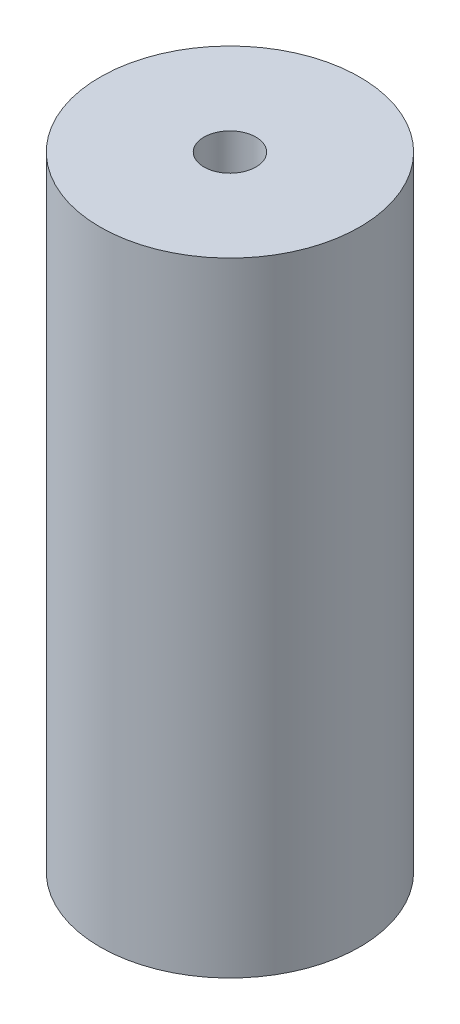
SolidWorks part; units mm, degrees
ref_plane "Plan de face" through (0, 0, 0) normal (0, 0, 1) x (1, 0, 0)
ref_plane "Plan de dessus" through (0, 0, 0) normal (0, 1, 0) x (1, 0, 0)
ref_plane "Plan de droite" through (0, 0, 0) normal (1, 0, 0) x (0, 0, -1)
sketch "Esquisse1" plane through (0, 0, 0) normal (0, 1, 0) x (1, 0, 0)
  circle A0 centre (0, 0) radius 12.5
  dimension "D1" = 25
extrude "Boss.-Extru.1" add sketch "Esquisse1" along normal blind 60
sketch "Esquisse2" plane through (0, 0, 0) normal (0, -1, 0) x (1, 0, 0)
  circle A0 centre (0, 0) radius 2.5
extrude "Enlèv. mat.-Extru.1" cut sketch "Esquisse2" against normal blind 60 contours A0
